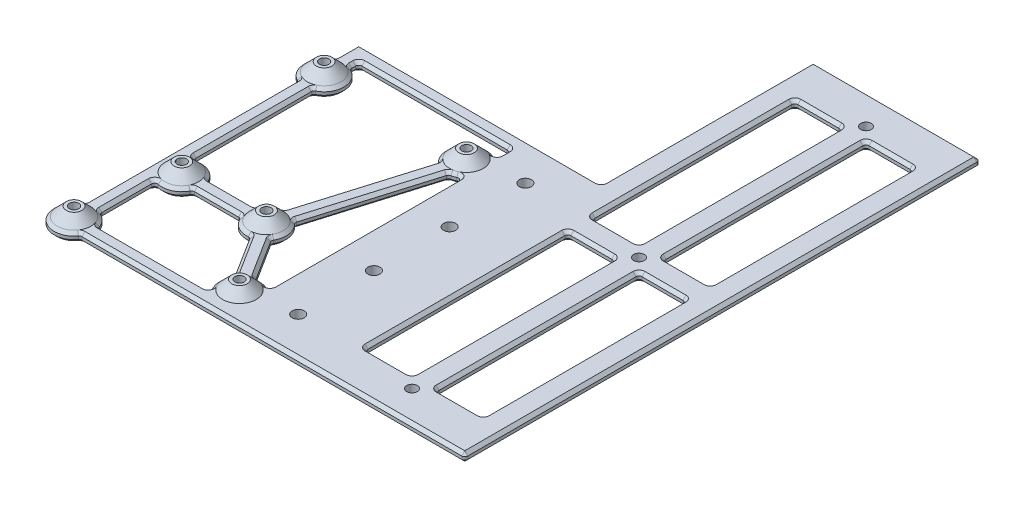
SolidWorks part; units mm, degrees
ref_plane "Front Plane" through (0, 0, 0) normal (0, 0, 1) x (1, 0, 0)
ref_plane "Top Plane" through (0, 0, 0) normal (0, 1, 0) x (1, 0, 0)
ref_plane "Right Plane" through (0, 0, 0) normal (1, 0, 0) x (0, 0, -1)
sketch "Sketch1" plane through (0, 0, 0) normal (0, 1, 0) x (1, 0, 0)
  line L0 (12.5, 0) -> (12.5, 100) construction
  line L1 (-12.5, 0) -> (12.5, 0)
  line L2 (-12.5, 0) -> (-12.5, 100) construction
  line L3 (-12.5, 100) -> (12.5, 100)
  line L4 (67.5, 85) -> (12.5, 85) construction
  line L5 (-67.5, 100) -> (-12.5, 100)
  line L6 (-67.5, 100) -> (-67.5, 92.0675)
  line L7 (-59.4109, 0) -> (-12.5, 0)
  line L8 (40, 159.93) -> (40, 10.07) construction
  line L9 (12.5, 0) -> (67.5, 0)
  line L10 (12.5, 100) -> (12.5, 170)
  line L11 (12.5, 170) -> (67.5, 170)
  line L12 (67.5, 0) -> (67.5, 170)
  line L13 (-58.5888, 5) -> (-21.1242, 5)
  line L14 (-62.5, 95) -> (-62.5, 92.1005)
  line L15 (-62.5, 95) -> (-12.5, 95)
  line L16 (-62.5, 79.9595) -> (-62.5, 39.9632)
  line L17 (-62.5, 95) -> (-62.5, 5) construction
  line L18 (-62.5, 27.9568) -> (-62.5, 9.5505)
  line L19 (-62.5, 5) -> (-12.5, 5) construction
  line L20 (-31.94, 33.96) -> (-16.7, 9.83) construction
  line L21 (-16.7, 84.76) -> (-31.94, 33.96) construction
  line L22 (-31.94, 33.96) -> (-59.88, 33.96) construction
  line L23 (-53.8259, 36.46) -> (-37.9941, 36.46)
  line L24 (-53.8259, 31.46) -> (-37.9941, 31.46)
  line L25 (-30.8209, 27.5063) -> (-22.0466, 13.6137)
  line L26 (-26.5934, 30.1763) -> (-17.8191, 16.2837)
  line L27 (-27.8058, 39.0404) -> (-16.0451, 78.2428)
  line L28 (-32.5949, 40.4772) -> (-20.8342, 79.6796)
  line L29 (-45.91, 36.46) -> (-45.91, 31.46) construction
  line L30 (-26.4337, 20.56) -> (-22.2063, 23.23) construction
  line L31 (-26.7146, 60.0784) -> (-21.9254, 58.6416) construction
  line L32 (-12.5, 14.8562) -> (-12.5, 79.7338)
  line L33 (-12.5, 89.7862) -> (-12.5, 95)
  line L34 (-67.5, 79.9925) -> (-67.5, 9.5175)
  line L35 (-67.5, 100) -> (-67.5, 0) construction
  line L36 (-67.5, 0) -> (-12.5, 0) construction
  line L37 (0, 0) -> (0, 100) construction
  line L38 (-12.5, 50) -> (12.5, 50) construction
  line L39 (2, 62.5) -> (2, 37.5) construction
  line L40 (2, 62.5) -> (2, 87.5) construction
  line L41 (2, 112.5) -> (2, 87.5) construction
  line L42 (59.5, 14.07) -> (44, 14.07)
  line L43 (20.5, 155.93) -> (36, 155.93)
  line L44 (20.5, 155.93) -> (20.5, 89)
  line L45 (20.5, 14.07) -> (36, 14.07)
  line L46 (36, 155.93) -> (36, 89)
  line L47 (59.5, 155.93) -> (59.5, 89)
  line L48 (59.5, 155.93) -> (44, 155.93)
  line L49 (44, 155.93) -> (44, 89)
  line L50 (59.5, 81) -> (59.5, 14.07)
  line L51 (20.5, 81) -> (36, 81)
  line L52 (44, 89) -> (36, 89) construction
  line L53 (20.5, 89) -> (36, 89)
  line L54 (20.5, 81) -> (20.5, 14.07)
  line L55 (44, 89) -> (59.5, 89)
  line L56 (36, 81) -> (36, 89) construction
  line L57 (44, 81) -> (59.5, 81)
  line L58 (44, 81) -> (44, 14.07)
  line L59 (36, 81) -> (36, 14.07)
  circle A0 centre (-64.96, 86.03) radius 1.55
  circle A1 centre (-59.88, 33.96) radius 1.55
  circle A2 centre (-64.96, 3.48) radius 1.55
  circle A3 centre (-16.7, 84.76) radius 1.55
  circle A4 centre (-16.7, 9.83) radius 1.55
  circle A5 centre (-31.94, 33.96) radius 1.55
  circle A6 centre (40, 159.93) radius 1.75
  circle A7 centre (40, 85) radius 1.75
  circle A8 centre (40, 10.07) radius 1.75
  arc A9 (-58.5888, 5) -> (-62.5, 9.5505) centre (-64.96, 3.48) ccw
  arc A10 (-62.5, 79.9595) -> (-62.5, 92.1005) centre (-64.96, 86.03) ccw
  arc A11 (-62.5, 27.9568) -> (-53.8259, 31.46) centre (-59.88, 33.96) ccw
  arc A12 (-37.9941, 31.46) -> (-30.8209, 27.5063) centre (-31.94, 33.96) ccw
  arc A13 (-16.0451, 78.2428) -> (-12.5, 79.7338) centre (-16.7, 84.76) ccw
  arc A14 (-12.5, 14.8562) -> (-17.8191, 16.2837) centre (-16.7, 9.83) ccw
  circle A15 centre (-64.96, 86.03) radius 6.55 construction
  circle A16 centre (-64.96, 3.48) radius 6.55 construction
  circle A17 centre (-59.88, 33.96) radius 6.55 construction
  circle A18 centre (-16.7, 9.83) radius 6.55 construction
  arc A19 (-53.8259, 36.46) -> (-62.5, 39.9632) centre (-59.88, 33.96) ccw
  circle A20 centre (-31.94, 33.96) radius 6.55 construction
  arc A21 (-26.5934, 30.1763) -> (-27.8058, 39.0404) centre (-31.94, 33.96) ccw
  arc A22 (-32.5949, 40.4772) -> (-37.9941, 36.46) centre (-31.94, 33.96) ccw
  arc A23 (-22.0466, 13.6137) -> (-21.1242, 5) centre (-16.7, 9.83) ccw
  circle A24 centre (-16.7, 84.76) radius 6.55 construction
  arc A25 (-12.5, 89.7862) -> (-20.8342, 79.6796) centre (-16.7, 84.76) ccw
  arc A26 (-67.5, 79.9925) -> (-67.5, 92.0675) centre (-64.96, 86.03) cw
  arc A27 (-59.4109, 0) -> (-67.5, 9.5175) centre (-64.96, 3.48) cw
  circle A28 centre (0, 87.5) radius 2
  circle A29 centre (0, 62.5) radius 2
  circle A30 centre (0, 37.5) radius 2
  circle A31 centre (0, 12.5) radius 2
  point P27 (40, 85)
  point P97 (2, 100)
  dimension "D4" = 66.04
  dimension "D13" = 3.1
  dimension "D16" = 3.5
  dimension "D21" = 4
  dimension "D1" = 25
  dimension "D2" = 13.97
  dimension "D3" = 100
  dimension "D5" = 96.52
  dimension "D6" = 15.24
  dimension "D7" = 90.17
  dimension "D8" = 2.54
  dimension "D9" = 7.62
  dimension "D10" = 35.56
  dimension "D11" = 55
  dimension "D12" = 50.8
  dimension "D14" = 55
  dimension "D15" = 170
  dimension "D17" = 74.93
  dimension "D20" = 5
  dimension "D22" = 8
  dimension "D23" = 8
  dimension "D24" = 4
  dimension "D18" = 5
  dimension "D19" = 5
extrude "Boss-Extrude1" add sketch "Sketch1" along normal blind 3 contours L12 L11 L10 L3 L5 L6 A26 L34 A27 L7 L1 L9
fillet "Fillet1" radius 1 49 edges at (-22.0466, 1.5, -13.6137) (-30.8209, 1.5, -27.5063) (-37.9941, 1.5, -31.46) (-53.8259, 1.5, -31.46) (-62.5, 1.5, -27.9568) (-62.5, 1.5, -9.5505) (-58.5888, 1.5, -5) (-21.1242, 1.5, -5) (-12.5, 1.5, -14.8562) (-12.5, 1.5, -79.7338) (-27.8058, 1.5, -39.0404) (-26.5934, 1.5, -30.1763) (-17.8191, 1.5, -16.2837) (-53.8259, 1.5, -36.46) (-37.9941, 1.5, -36.46) (-32.5949, 1.5, -40.4772) (-20.8342, 1.5, -79.6796) (-12.5, 1.5, -89.7862) (-12.5, 1.5, -95) (-62.5, 1.5, -95) (-62.5, 1.5, -92.1005) (-62.5, 1.5, -79.9595) (-62.5, 1.5, -39.9632) (-16.0451, 1.5, -78.2428) (67.5, 1.5, 0) (67.5, 1.5, -170) (12.5, 1.5, -170) (-67.5, 1.5, -100) (-67.5, 1.5, -92.0675) (12.5, 1.5, -100) (-67.5, 1.5, -79.9925) (-67.5, 1.5, -9.5175) (-59.4109, 1.5, 0) (44, 1.5, -155.93) (44, 1.5, -89) (59.5, 1.5, -89) (59.5, 1.5, -155.93) (36, 1.5, -81) (20.5, 1.5, -81) (20.5, 1.5, -14.07) (36, 1.5, -14.07) (20.5, 1.5, -89) (36, 1.5, -89) (36, 1.5, -155.93) (59.5, 1.5, -81) (44, 1.5, -81) (44, 1.5, -14.07) (59.5, 1.5, -14.07) (20.5, 1.5, -155.93)
chamfer "Chamfer1" distance 1 angle 45 196 edges at (-40.5247, 0, -5) (-60.025, 0, -7.7868) (-67.5, 0, -95.8493) (-71.51, 0, -86.03) (-67.5, 0, -44.755) (-27.5, 0, -100) (12.5, 0, -135) (40, 0, -170) (67.5, 0, -85) (-69.9197, 0, 0.7984) (3.8086, 0, 0) (-35.1017, 0, -28.2236) (-38.1118, 0, -31.3154) (-30.8802, 0, -27.3296) (-45.91, 0, -31.46) (-26.4337, 0, -20.56) (-53.7082, 0, -31.3154) (-22.2317, 0, -13.636) (-57.1123, 0, -28.0235) (-23.25, 0, -9.8085) (-62.1267, 0, -27.3651) (-22.3383, 0, -5.5037) (-62.5, 0, -18.3882) (-62.3539, 0, -9.6701) (-58.4201, 0, -5.1834) (-25.4504, 0, -34.8476) (-26.4083, 0, -30.154) (-27.6335, 0, -39.1116) (-22.2063, 0, -23.23) (-21.9254, 0, -58.6416) (-17.7598, 0, -16.4604) (-15.9404, 0, -78.0885) (-15.539, 0, -16.2763) (-14.6761, 0, -78.5305) (-12.9633, 0, -15.8246) (-12.9633, 0, -78.7654) (-12.5, 0, -47.295) (-45.91, 0, -36.46) (-38.1118, 0, -36.6046) (-53.7082, 0, -36.6046) (-35.8499, 0, -39.215) (-57.1123, 0, -39.8965) (-32.6996, 0, -40.6315) (-62.1267, 0, -40.5549) (-26.7146, 0, -60.0784) (-62.5, 0, -60.3268) (-21.0065, 0, -79.6084) (-62.3539, 0, -79.8399) (-22.0852, 0, -88.4885) (-58.41, 0, -86.03) (-12.9633, 0, -90.7546) (-62.3539, 0, -92.2201) (-12.5, 0, -92.7992) (-62.5, 0, -93.3703) (-12.7929, 0, -94.7071) (-62.2071, 0, -94.7071) (-37.5, 0, -95) (67.5, 3, -85) (40, 3, -170) (12.5, 3, -135) (-27.5, 3, -100) (-67.5, 3, -95.8493) (-71.51, 3, -86.03) (-67.5, 3, -44.755) (-69.9197, 3, 0.7984) (3.8086, 3, 0) (-15.539, 3, -16.2763) (-12.9633, 3, -15.8246) (-17.7598, 3, -16.4604) (-12.5, 3, -47.295) (-22.2063, 3, -23.23) (-12.9633, 3, -78.7654) (-26.4083, 3, -30.154) (-14.6761, 3, -78.5305) (-25.4504, 3, -34.8476) (-15.9404, 3, -78.0885) (-27.6335, 3, -39.1116) (-21.9254, 3, -58.6416) (-23.25, 3, -9.8085) (-22.2317, 3, -13.636) (-22.3383, 3, -5.5037) (-26.4337, 3, -20.56) (-40.5247, 3, -5) (-30.8802, 3, -27.3296) (-58.4201, 3, -5.1834) (-35.1017, 3, -28.2236) (-60.025, 3, -7.7868) (-38.1118, 3, -31.3154) (-62.3539, 3, -9.6701) (-45.91, 3, -31.46) (-62.5, 3, -18.3882) (-53.7082, 3, -31.3154) (-62.1267, 3, -27.3651) (-57.1123, 3, -28.0235) (-58.41, 3, -86.03) (-62.3539, 3, -79.8399) (-62.3539, 3, -92.2201) (-62.5, 3, -60.3268) (-62.5, 3, -93.3703) (-62.1267, 3, -40.5549) (-62.2071, 3, -94.7071) (-57.1123, 3, -39.8965) (-37.5, 3, -95) (-53.7082, 3, -36.6046) (-12.7929, 3, -94.7071) (-45.91, 3, -36.46) (-12.5, 3, -92.7992) (-38.1118, 3, -36.6046) (-12.9633, 3, -90.7546) (-35.8499, 3, -39.215) (-22.0852, 3, -88.4885) (-32.6996, 3, -40.6315) (-21.0065, 3, -79.6084) (-26.7146, 3, -60.0784) (-67.2071, 3, -99.7071) (-67.643, 3, -92.1833) (12.2071, 3, -100.2929) (-67.643, 3, -79.8767) (12.7929, 3, -169.7071) (-67.643, 3, -9.6333) (67.2071, 3, -169.7071) (-59.3337, 3, 0.1074) (67.2071, 3, -0.2929) (-67.2071, 0, -99.7071) (-67.643, 0, -92.1833) (12.2071, 0, -100.2929) (-67.643, 0, -79.8767) (12.7929, 0, -169.7071) (-67.643, 0, -9.6333) (67.2071, 0, -169.7071) (-59.3337, 0, 0.1074) (67.2071, 0, -0.2929) (51.75, 3, -89) (59.2071, 3, -89.2929) (44.2929, 3, -89.2929) (59.5, 3, -122.465) (44, 3, -122.465) (59.2071, 3, -155.6371) (44.2929, 3, -155.6371) (51.75, 3, -155.93) (28.25, 3, -89) (35.7071, 3, -89.2929) (20.7929, 3, -89.2929) (36, 3, -122.465) (20.5, 3, -122.465) (35.7071, 3, -155.6371) (20.7929, 3, -155.6371) (28.25, 3, -155.93) (51.75, 3, -14.07) (59.2071, 3, -14.3629) (44.2929, 3, -14.3629) (59.5, 3, -47.535) (44, 3, -47.535) (59.2071, 3, -80.7071) (44.2929, 3, -80.7071) (51.75, 3, -81) (28.25, 3, -14.07) (35.7071, 3, -14.3629) (20.7929, 3, -14.3629) (36, 3, -47.535) (20.5, 3, -47.535) (35.7071, 3, -80.7071) (20.7929, 3, -80.7071) (28.25, 3, -81) (20.5, 0, -122.465) (20.7929, 0, -89.2929) (20.7929, 0, -155.6371) (28.25, 0, -89) (28.25, 0, -155.93) (35.7071, 0, -89.2929) (35.7071, 0, -155.6371) (36, 0, -122.465) (20.5, 0, -47.535) (20.7929, 0, -14.3629) (20.7929, 0, -80.7071) (28.25, 0, -14.07) (28.25, 0, -81) (35.7071, 0, -14.3629) (35.7071, 0, -80.7071) (36, 0, -47.535) (59.5, 0, -47.535) (59.2071, 0, -80.7071) (59.2071, 0, -14.3629) (51.75, 0, -81) (51.75, 0, -14.07) (44.2929, 0, -80.7071) (44.2929, 0, -14.3629) (44, 0, -47.535) (59.5, 0, -122.465) (59.2071, 0, -155.6371) (59.2071, 0, -89.2929) (51.75, 0, -155.93) (51.75, 0, -89) (44.2929, 0, -155.6371) (44.2929, 0, -89.2929) (44, 0, -122.465)
sketch "Sketch2" plane through (0, 3, 0) normal (0, 1, 0) x (1, 0, 0)
  line L0 (9.5, 16.9797) -> (9.5, 87.5) construction
  line L2 (0, 87.5) -> (9.5, 87.5) construction
  line L3 (11.5, 100) -> (11.5, 99) construction
  text T0 "Azul" font "Arial Rounded MT Bold" height 19
  dimension "D1" = 2
extrude "Cut-Extrude1" [suppressed] cut sketch "Sketch2" against normal blind 1.5
sketch "Sketch3" plane through (0, 3, 0) normal (0, 1, 0) x (1, 0, 0)
  circle A0 centre (-64.96, 3.48) radius 5.55
  circle A1 centre (-59.88, 33.96) radius 5.55
  circle A2 centre (-31.94, 33.96) radius 5.55
  circle A3 centre (-16.7, 9.83) radius 5.55
  circle A4 centre (-16.7, 84.76) radius 5.55
  circle A5 centre (-64.96, 86.03) radius 5.55
  arc A6 (-14.3477, 89.7868) -> (-20.5774, 80.7891) centre (-16.7, 84.76) ccw construction
  circle A7 centre (-64.96, 86.03) radius 1.55
  circle A8 centre (-16.7, 84.76) radius 1.55
  circle A9 centre (-31.94, 33.96) radius 1.55
  circle A10 centre (-59.88, 33.96) radius 1.55
  circle A11 centre (-16.7, 9.83) radius 1.55
  circle A12 centre (-64.96, 3.48) radius 1.55
extrude "Boss-Extrude2" add sketch "Sketch3" along normal blind 3
chamfer "Chamfer2" distance 3 angle 45 6 edges at (-64.96, 6, -80.48) (-16.7, 6, -79.21) (-16.7, 6, -4.28) (-31.94, 6, -28.41) (-59.88, 6, -28.41) (-64.96, 6, 2.07)
